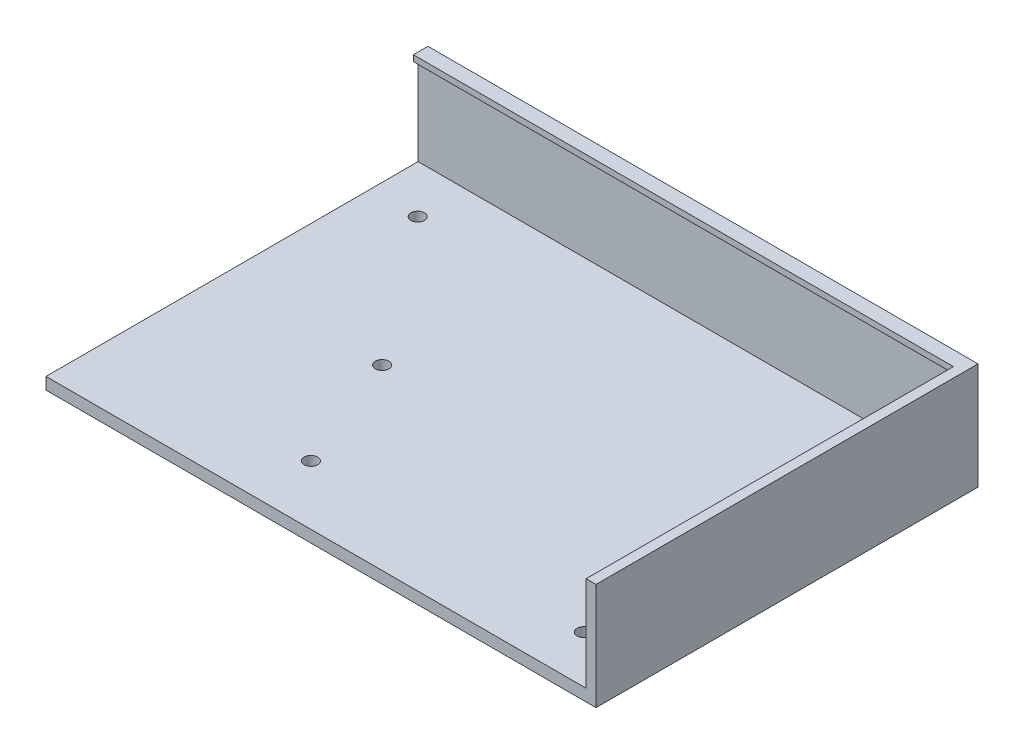
SolidWorks part; units mm, degrees
ref_plane "Front Plane" through (0, 0, 0) normal (0, 0, 1) x (1, 0, 0)
ref_plane "Top Plane" through (0, 0, 0) normal (0, 1, 0) x (1, 0, 0)
ref_plane "Right Plane" through (0, 0, 0) normal (1, 0, 0) x (0, 0, -1)
sketch "Sketch1" plane through (0, 0, 0) normal (0, 1, 0) x (1, 0, 0)
  line L1 (-139.1, -96.6) -> (139.1, -96.6)
  line L2 (-139.1, -96.6) -> (-139.1, 96.6)
  line L3 (-139.1, 96.6) -> (139.1, 96.6)
  line L4 (139.1, -96.6) -> (139.1, 96.6)
  line L5 (-139.1, -96.6) -> (139.1, 96.6) construction
  line L6 (-139.1, 96.6) -> (139.1, -96.6) construction
  dimension "D1" = 278.2
  dimension "D2" = 193.2
extrude "Shell Block" add sketch "Sketch1" along normal blind 27
ref_plane "Shell Front" through (0, 27, 0) normal (0, 1, 0) x (1, 0, 0)
sketch "Sketch2" plane through (0, 27, 0) normal (0, 1, 0) x (1, 0, 0)
  line L1 (-136.6, -92.9) -> (136.6, -92.9)
  line L2 (-136.6, -92.9) -> (-136.6, 92.9)
  line L3 (-136.6, 92.9) -> (136.6, 92.9)
  line L4 (136.6, -92.9) -> (136.6, 92.9)
  line L5 (-136.6, -92.9) -> (136.6, 92.9) construction
  line L6 (-136.6, 92.9) -> (136.6, -92.9) construction
  dimension "D1" = 273.2
  dimension "D2" = 185.8
extrude "Front Opening" cut sketch "Sketch2" against normal blind 1.5
ref_plane "Under Lip" through (0, 25.5, 0) normal (0, 1, 0) x (1, 0, 0)
sketch "Sketch3" plane through (0, 25.5, 0) normal (0, 1, 0) x (1, 0, 0)
  line L1 (-136.6, -94.1) -> (136.6, -94.1)
  line L2 (-136.6, -94.1) -> (-136.6, 94.1)
  line L3 (-136.6, 94.1) -> (136.6, 94.1)
  line L4 (136.6, -94.1) -> (136.6, 94.1)
  line L5 (-136.6, -94.1) -> (136.6, 94.1) construction
  line L6 (-136.6, 94.1) -> (136.6, -94.1) construction
  dimension "D1" = 273.2
  dimension "D2" = 188.2
extrude "Display Pocket" cut sketch "Sketch3" against normal blind 22.5
ref_plane "Back Inner" through (0, 3, 0) normal (0, 1, 0) x (1, 0, 0)
sketch "Sketch4" plane through (0, 3, 0) normal (0, 1, 0) x (1, 0, 0)
  line L1 (-69, 28) -> (-66, 28)
  line L2 (-69, 28) -> (-69, 84)
  line L3 (-69, 84) -> (-66, 84)
  line L4 (-66, 28) -> (-66, 84)
  line L6 (-69, -84) -> (-66, -84)
  line L7 (-69, -84) -> (-69, -28)
  line L8 (-69, -28) -> (-66, -28)
  line L9 (-66, -84) -> (-66, -28)
  line L11 (-77, 28) -> (-74, 28)
  line L12 (-77, 28) -> (-77, 84)
  line L13 (-77, 84) -> (-74, 84)
  line L14 (-74, 28) -> (-74, 84)
  line L16 (-77, -84) -> (-74, -84)
  line L17 (-77, -84) -> (-77, -28)
  line L18 (-77, -28) -> (-74, -28)
  line L19 (-74, -84) -> (-74, -28)
  line L21 (-85, 28) -> (-82, 28)
  line L22 (-85, 28) -> (-85, 84)
  line L23 (-85, 84) -> (-82, 84)
  line L24 (-82, 28) -> (-82, 84)
  line L26 (-85, -84) -> (-82, -84)
  line L27 (-85, -84) -> (-85, -28)
  line L28 (-85, -28) -> (-82, -28)
  line L29 (-82, -84) -> (-82, -28)
  line L31 (-93, 28) -> (-90, 28)
  line L32 (-93, 28) -> (-93, 84)
  line L33 (-93, 84) -> (-90, 84)
  line L34 (-90, 28) -> (-90, 84)
  line L36 (-93, -84) -> (-90, -84)
  line L37 (-93, -84) -> (-93, -28)
  line L38 (-93, -28) -> (-90, -28)
  line L39 (-90, -84) -> (-90, -28)
  line L41 (-101, 28) -> (-98, 28)
  line L42 (-101, 28) -> (-101, 84)
  line L43 (-101, 84) -> (-98, 84)
  line L44 (-98, 28) -> (-98, 84)
  line L46 (-101, -84) -> (-98, -84)
  line L47 (-101, -84) -> (-101, -28)
  line L48 (-101, -28) -> (-98, -28)
  line L49 (-98, -84) -> (-98, -28)
  line L51 (-109, 28) -> (-106, 28)
  line L52 (-109, 28) -> (-109, 84)
  line L53 (-109, 84) -> (-106, 84)
  line L54 (-106, 28) -> (-106, 84)
  line L56 (-109, -84) -> (-106, -84)
  line L57 (-109, -84) -> (-109, -28)
  line L58 (-109, -28) -> (-106, -28)
  line L59 (-106, -84) -> (-106, -28)
  line L61 (-117, 28) -> (-114, 28)
  line L62 (-117, 28) -> (-117, 84)
  line L63 (-117, 84) -> (-114, 84)
  line L64 (-114, 28) -> (-114, 84)
  line L66 (-117, -84) -> (-114, -84)
  line L67 (-117, -84) -> (-117, -28)
  line L68 (-117, -28) -> (-114, -28)
  line L69 (-114, -84) -> (-114, -28)
  line L71 (-125, 28) -> (-122, 28)
  line L72 (-125, 28) -> (-125, 84)
  line L73 (-125, 84) -> (-122, 84)
  line L74 (-122, 28) -> (-122, 84)
  line L76 (-125, -84) -> (-122, -84)
  line L77 (-125, -84) -> (-125, -28)
  line L78 (-125, -28) -> (-122, -28)
  line L79 (-122, -84) -> (-122, -28)
extrude "Vent Slots" cut sketch "Sketch4" against normal blind 4
sketch "Sketch5" plane through (0, 0, 0) normal (1, 0, 0) x (0, 0, -1)
  line L1 (-29, 5) -> (29, 5)
  line L2 (-29, 5) -> (-29, 21)
  line L3 (-29, 21) -> (29, 21)
  line L4 (29, 5) -> (29, 21)
extrude "Cable Exit (-X short side)" cut sketch "Sketch5" against normal blind 140.1
sketch "Sketch6" plane through (0, 3, 0) normal (0, 1, 0) x (1, 0, 0)
  circle A0 centre (-40, -45) radius 1.7
  circle A1 centre (-40, 45) radius 1.7
  circle A2 centre (40, -45) radius 1.7
  circle A3 centre (40, 45) radius 1.7
  circle A4 centre (-52, -15) radius 1.7
  circle A5 centre (-52, 15) radius 1.7
  circle A6 centre (52, -15) radius 1.7
  circle A7 centre (52, 15) radius 1.7
  circle A8 centre (-12, -82) radius 1.7
  circle A9 centre (-12, 82) radius 1.7
  circle A10 centre (12, -82) radius 1.7
  circle A11 centre (12, 82) radius 1.7
  circle A12 centre (-124, -12) radius 1.7
  circle A13 centre (-124, 12) radius 1.7
  circle A14 centre (124, -12) radius 1.7
  circle A15 centre (124, 12) radius 1.7
  circle A16 centre (-72, 12) radius 1.7
  circle A17 centre (-72, -12) radius 1.7
extrude "Bolt Holes" cut sketch "Sketch6" against normal blind 4
sketch "Sketch7" plane through (0, 0, 0) normal (0, 1, 0) x (1, 0, 0)
  line L1 (-200, -200) -> (0, -200)
  line L2 (-200, -200) -> (-200, 200)
  line L3 (-200, 200) -> (0, 200)
  line L4 (0, -200) -> (0, 200)
extrude "Keep one half (X)" cut sketch "Sketch7" against normal through all and the other way through all
sketch "Sketch8" plane through (0, 0, 0) normal (0, 1, 0) x (1, 0, 0)
  line L1 (-200, 0) -> (200, 0)
  line L2 (-200, 0) -> (-200, -200)
  line L3 (-200, -200) -> (200, -200)
  line L4 (200, 0) -> (200, -200)
extrude "Keep one quarter (Z)" cut sketch "Sketch8" against normal through all and the other way through all
equation "\"DispL\"= 272.0"
equation "\"DispW\"= 187.0"
equation "\"DispT\"= 20.0"
equation "\"Clr\"= 0.6"
equation "\"Wall\"= 2.5"
equation "\"BackT\"= 3.0"
equation "\"CableRoom\"= 4.0"
equation "\"LipW\"= 1.2"
equation "\"LipT\"= 1.5"
equation "\"CableW\"= 58.0"
equation "\"CableH\"= 16.0"
equation "\"BoltD\"= 3.4"
equation "\"ShellL\"= \"DispL\" + 2 * \"Clr\" + 2 * \"Wall\""
equation "\"ShellW\"= \"DispW\" + 2 * \"Clr\" + 2 * \"Wall\""
equation "\"ShellH\"= \"BackT\" + \"DispT\" + \"CableRoom\""
equation "\"D1@Sketch1\" = \"ShellL\""
equation "\"D2@Sketch1\" = \"ShellW\""
equation "\"D1@Shell Block\" = \"ShellH\""
equation "\"D1@Shell Front\" = \"ShellH\""
equation "\"D1@Sketch2\" = \"DispL\" + 2 * \"Clr\""
equation "\"D2@Sketch2\" = \"DispW\" + 2 * \"Clr\" - 2 * \"LipW\""
equation "\"D1@Front Opening\" = \"LipT\""
equation "\"D1@Under Lip\" = \"ShellH\" - \"LipT\""
equation "\"D1@Sketch3\" = \"DispL\" + 2 * \"Clr\""
equation "\"D2@Sketch3\" = \"DispW\" + 2 * \"Clr\""
equation "\"D1@Display Pocket\" = \"ShellH\" - \"LipT\" - \"BackT\""
equation "\"D1@Back Inner\" = \"BackT\""
